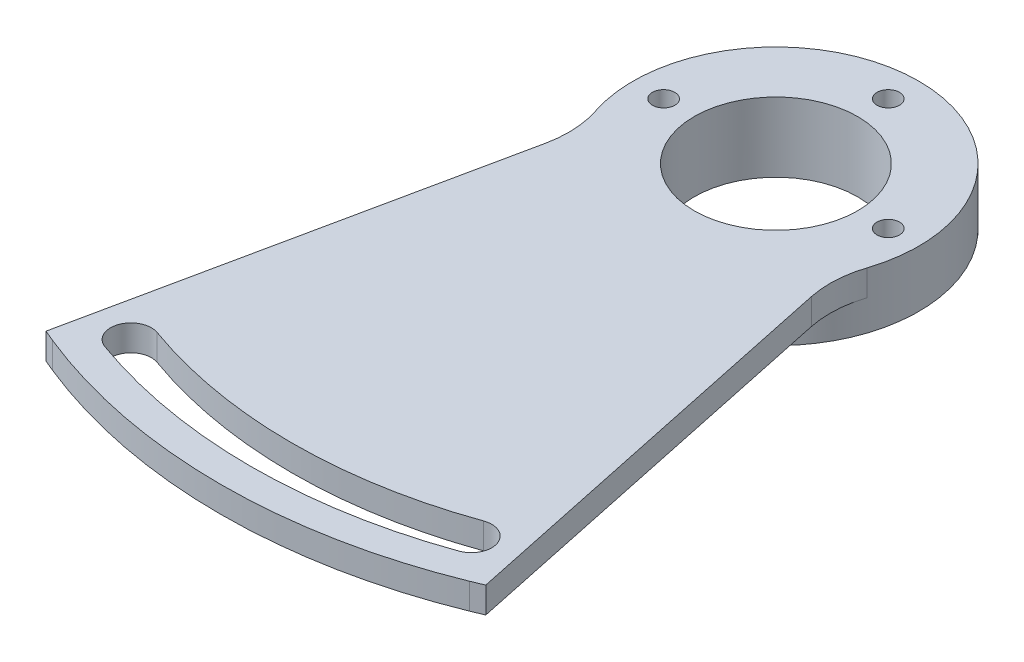
SolidWorks part; units mm, degrees
ref_plane "Front Plane" through (0, 0, 0) normal (0, 0, 1) x (1, 0, 0)
ref_plane "Top Plane" through (0, 0, 0) normal (0, 1, 0) x (1, 0, 0)
ref_plane "Right Plane" through (0, 0, 0) normal (1, 0, 0) x (0, 0, -1)
sketch "Sketch1" plane through (0, 0, 0) normal (0, 1, 0) x (1, 0, 0)
  line L0 (7.2, -9.7213) -> (0, -9.7213) construction
  line L1 (21.5362, -59.6749) -> (20.4111, -60.1451)
  line L2 (-21.5362, -59.6749) -> (-20.4111, -60.1451)
  line L5 (19.421, -49.6466) -> (11, -9.7213)
  line L6 (-19.421, -49.6466) -> (-11, -9.7213)
  line L7 (4.5, -9.7213) -> (8, -9.7213) construction
  line L8 (8, -9.7213) -> (14, -9.7213) construction
  line L10 (-0.0056, -54.1196) -> (-0.0012, -57.1196) construction
  line L11 (-0.0012, -57.1196) -> (-0.0003, -61.1196) construction
  line L12 (-0.0003, -61.1196) -> (0, -64.1196) construction
  line L13 (-0.0012, -57.1196) -> (-0.0003, -61.1196) construction
  line L15 (0, -9.7213) -> (-20.4111, -60.1451) construction
  line L16 (0, -9.7213) -> (20.4111, -60.1451) construction
  line L17 (19.421, -49.6466) -> (21.5362, -59.6749)
  line L18 (-19.421, -49.6466) -> (-21.5362, -59.6749)
  line L19 (-20.4111, -60.1451) -> (-16.659, -50.8757)
  line L20 (20.4111, -60.1451) -> (16.659, -50.8757)
  arc A3 (19.421, -49.6466) -> (-19.4311, -49.6417) centre (0, -9.7213) cw
  circle A4 centre (0, -9.7213) radius 8
  arc A7 (-0.0012, -57.1196) -> (19.7205, -52.8223) centre (0, -9.7213) ccw
  arc A8 (-0.0003, -61.1196) -> (20.1163, -57.0195) centre (0, -9.7213) ccw
  arc A9 (0, -64.1196) -> (20.4111, -60.1451) centre (0, -9.7213) ccw
  arc A11 (0, -64.1196) -> (-20.4111, -60.1451) centre (0, -9.7213) cw
  arc A12 (0.0003, -61.1196) -> (-20.1163, -57.0195) centre (0, -9.7213) cw
  arc A13 (0.0012, -57.1196) -> (-19.7205, -52.8223) centre (0, -9.7213) cw
  circle A16 centre (0, -9.7213) radius 8
  circle A17 centre (0, -9.7213) radius 14
  circle A18 centre (11, -9.7213) radius 1.1
  circle A20 centre (-11, -9.7213) radius 1.1
  circle A21 centre (0, 1.2787) radius 1.1
  circle A26 centre (0, -9.7213) radius 6
  circle A27 centre (16.666, -56.2233) radius 2
  circle A29 centre (-16.666, -56.2233) radius 2
  point P35 (0, -9.7213)
  point P37 (0, -9.7213)
  point P62 (0, -9.7213)
  dimension "D1" = 44.075
extrude "Boss-Extrude1" add sketch "Sketch1" along normal blind 2.54 contours A3 A13 A7 | A16 | L5 L6 A3 | A8 A12 A11 A9 | L5 L6 | L19 A3 L18 L2 | A29 L19 A12 | A29 A13 L19 | L17 A3 L20 L1 | A27 L20 A7 | A27 A8 L20 region at (19.3032, 0, 54.4134) region at (0, 0, 61.3387) region at (0, 0, 37.9836) region at (18.6812, 0, 57.1134) region at (0, 0, 23.3253) region at (0, 0, 54.5122) region at (17.5511, 0, 54.2198) region at (-19.3032, 0, 54.4134) region at (-18.6812, 0, 57.1134) region at (-17.5511, 0, 54.2198)
fillet "Fillet2" radius 10 2 edges at (-12.3792, 1.27, 16.2601) (12.3792, 1.27, 16.2601)
extrude "Boss-Extrude2" add sketch "Sketch1<4>" against normal blind 3 contours A20 A17 A18 A21 A4 region at (0, 0, 23.3253)
sketch "Sketch1<4>" plane through (0, 0, 0) normal (0, 1, 0) x (1, 0, 0) same geometry as "Sketch1"
sketch "Sketch2" plane through (0, -3, 0) normal (0, -1, 0) x (1, 0, 0)
  circle A0 centre (0, 9.7213) radius 9
  circle A1 centre (0, 9.7213) radius 8
extrude "Boss-Extrude3" add sketch "Sketch2" along normal blind 1.27
